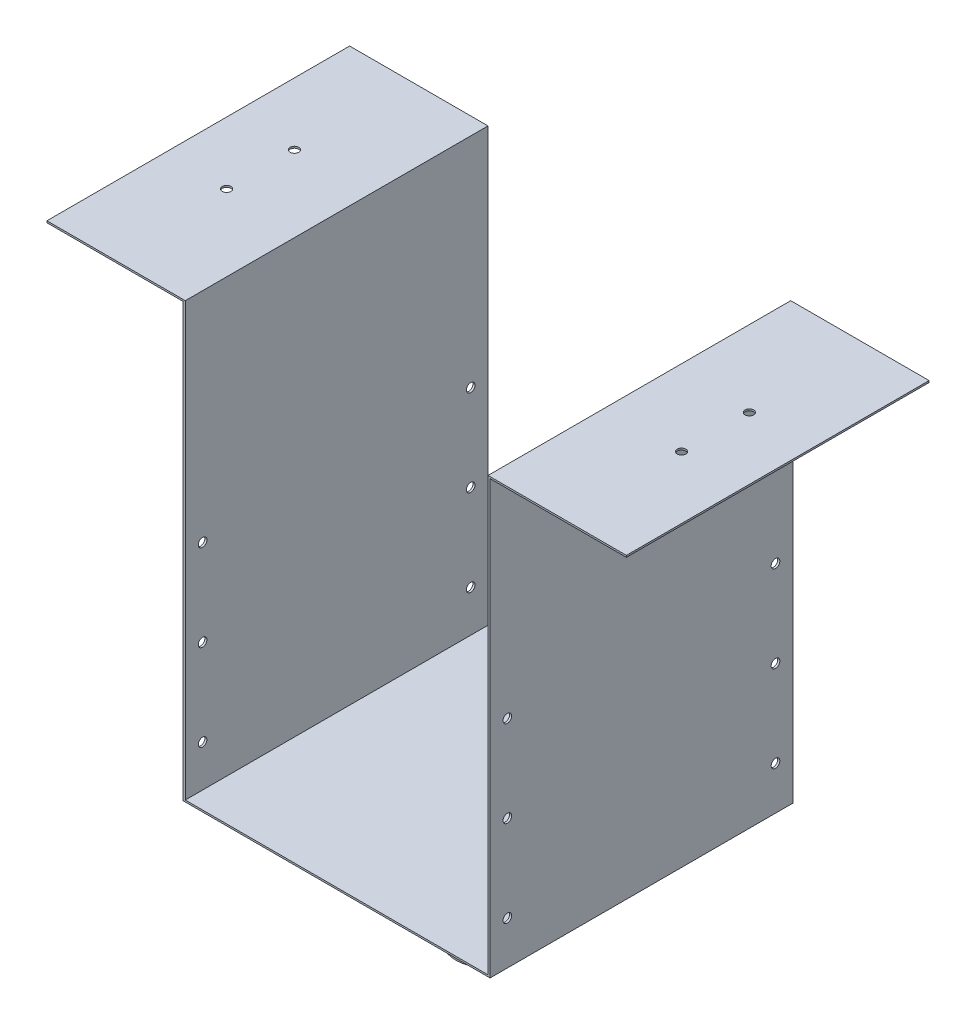
SolidWorks part; units mm, degrees
ref_plane "Front Plane" through (0, 0, 0) normal (0, 0, 1) x (1, 0, 0)
ref_plane "Top Plane" through (0, 0, 0) normal (0, 1, 0) x (1, 0, 0)
ref_plane "Right Plane" through (0, 0, 0) normal (1, 0, 0) x (0, 0, -1)
sketch "Sketch1" plane through (0, 0, 0) normal (0, 1, 0) x (1, 0, 0)
  line L1 (-87.5, -87.5) -> (87.5, -87.5)
  line L2 (-87.5, -87.5) -> (-87.5, 87.5)
  line L3 (-87.5, 87.5) -> (87.5, 87.5)
  line L4 (87.5, -87.5) -> (87.5, 87.5)
  line L5 (-87.5, -87.5) -> (87.5, 87.5) construction
  line L6 (-87.5, 87.5) -> (87.5, -87.5) construction
  point P0 (0, 0)
  dimension "D1" = 175
extrude "Boss-Extrude1" add sketch "Sketch1" along normal blind 1
sketch "Sketch2" plane through (0, 0, 0) normal (0, -1, 0) x (1, 0, 0)
  line L0 (0, -87.5) -> (0, 87.5) construction
  line L1 (-87.5, -87.5) -> (-88.7, -87.5)
  line L2 (-87.5, -87.5) -> (-87.5, 87.5)
  line L3 (-87.5, 87.5) -> (-88.7, 87.5)
  line L4 (-88.7, -87.5) -> (-88.7, 87.5)
  line L5 (87.5, -87.5) -> (-87.5, -87.5) construction
  line L6 (-87.5, 87.5) -> (87.5, 87.5) construction
  line L7 (88.7, -87.5) -> (88.7, 87.5)
  line L8 (87.5, 87.5) -> (88.7, 87.5)
  line L9 (87.5, -87.5) -> (87.5, 87.5)
  line L10 (87.5, -87.5) -> (88.7, -87.5)
  dimension "D1" = 1.2
extrude "Boss-Extrude2" add sketch "Sketch2" against normal blind 250
sketch "Sketch3" plane through (0, 250, 0) normal (0, 1, 0) x (1, 0, 0)
  line L0 (0, 87.5) -> (0, -87.5) construction
  line L1 (-87.5, 87.5) -> (-167.5, 87.5)
  line L2 (-87.5, 87.5) -> (-87.5, -87.5)
  line L3 (-87.5, -87.5) -> (-167.5, -87.5)
  line L4 (-167.5, 87.5) -> (-167.5, -87.5)
  line L5 (87.5, 87.5) -> (-87.5, 87.5) construction
  line L6 (-87.5, -87.5) -> (87.5, -87.5) construction
  line L7 (167.5, 87.5) -> (167.5, -87.5)
  line L8 (87.5, -87.5) -> (167.5, -87.5)
  line L9 (87.5, 87.5) -> (87.5, -87.5)
  line L10 (87.5, 87.5) -> (167.5, 87.5)
  dimension "D1" = 80
extrude "Boss-Extrude3" add sketch "Sketch3" along normal blind 1
sketch "Sketch4" plane through (0, 251, 0) normal (0, 1, 0) x (1, 0, 0)
  line L0 (87.5, 0) -> (131.5, 0) construction
  line L1 (87.5, 0) -> (167.5, 0) construction
  line L2 (131.5, 0) -> (131.5, 19.6) construction
  line L3 (0, 87.5) -> (0, -87.5) construction
  line L4 (87.5, 87.5) -> (-87.5, 87.5) construction
  line L5 (-87.5, -87.5) -> (87.5, -87.5) construction
  line L6 (-131.5, 0) -> (-131.5, 19.6) construction
  line L7 (-87.5, 0) -> (-131.5, 0) construction
  circle A1 centre (131.5, 19.6) radius 2.5
  circle A2 centre (131.5, -19.6) radius 2.5
  circle A3 centre (-131.5, -19.6) radius 2.5
  circle A4 centre (-131.5, 19.6) radius 2.5
  dimension "D3" = 5
  dimension "D1" = 44
  dimension "D2" = 19.6
extrude "Cut-Extrude1" cut sketch "Sketch4" against normal blind 10
sketch "Sketch5" plane through (-88.7, 0, 0) normal (-1, 0, 0) x (0, 0, 1)
  line L0 (-87.5, 207.5) -> (87.5, 207.5) construction
  line L1 (-87.5, 250) -> (-87.5, 0) construction
  line L2 (87.5, 250) -> (87.5, 0) construction
  line L3 (-87.5, 177.5) -> (87.5, 177.5) construction
  line L4 (87.5, 250) -> (-87.5, 250) construction
  dimension "D1" = 42.5
  dimension "D2" = 30
sketch "Sketch6" plane through (88.7, 0, 0) normal (1, 0, 0) x (0, 0, -1)
  line L0 (87.5, 25) -> (77.5, 25) construction
  line L1 (87.5, 250) -> (87.5, 0) construction
  line L2 (87.5, 0) -> (-87.5, 0) construction
  line L3 (0, 0) -> (0, 150.606) construction
  circle A0 centre (77.5, 25) radius 2.5
  circle A1 centre (77.5, 75) radius 2.5
  circle A2 centre (77.5, 125) radius 2.5
  circle A3 centre (-77.5, 125) radius 2.5
  circle A4 centre (-77.5, 75) radius 2.5
  circle A5 centre (-77.5, 25) radius 2.5
  dimension "D2" = 5
  dimension "D1" = 25
  dimension "D4" = 10
  dimension "D3" = 3
extrude "Cut-Extrude2" cut sketch "Sketch6" against normal blind 300
sketch "Sketch7" plane through (0, 0, 0) normal (0, -1, 0) x (1, 0, 0)
  circle A0 centre (0, 0) radius 18.5
  circle A1 centre (0, 0) radius 12.5
  dimension "D1" = 37
  dimension "D2" = 25
extrude "Boss-Extrude4" add sketch "Sketch7" along normal blind 70
